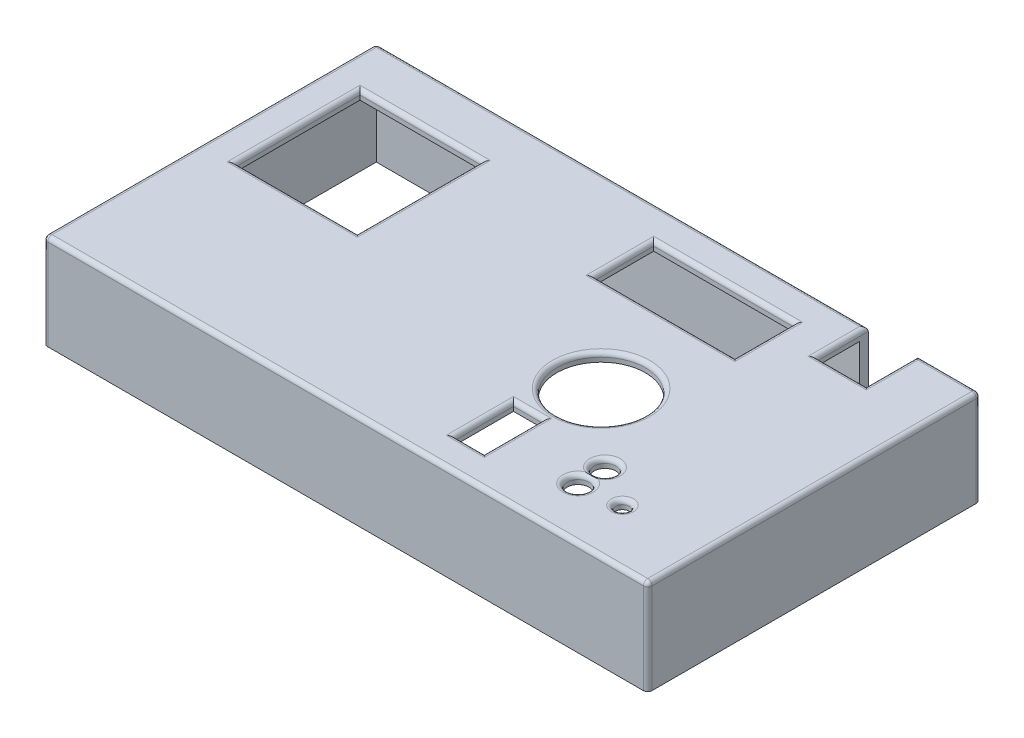
SolidWorks part; units mm, degrees
ref_plane "Front Plane" through (0, 0, 0) normal (0, 0, 1) x (1, 0, 0)
ref_plane "Top Plane" through (0, 0, 0) normal (0, 1, 0) x (1, 0, 0)
ref_plane "Right Plane" through (0, 0, 0) normal (1, 0, 0) x (0, 0, -1)
sketch "Sketch1" plane through (0, 0, 0) normal (0, 1, 0) x (1, 0, 0)
  line L0 (1.0429, 69.9365) -> (132.9972, 69.9365)
  line L1 (132.9972, 0.8484) -> (1.0429, 0.8484)
  line L2 (1.0429, 0.8484) -> (1.0429, 69.8095)
  line L3 (132.9972, 69.8095) -> (132.9972, 0.8484)
  line L4 (94.6421, 48.4741) -> (94.8961, 48.4741)
  line L5 (89.5621, 48.4741) -> (89.3081, 48.4741)
  line L6 (94.6421, 48.4741) -> (94.6421, 47.7121)
  line L7 (94.6421, 49.2361) -> (94.6421, 48.4741)
  line L8 (89.5621, 49.2361) -> (94.6421, 49.2361)
  line L9 (89.5621, 48.4741) -> (89.5621, 49.2361)
  line L10 (89.5621, 47.7121) -> (89.5621, 48.4741)
  line L11 (94.6421, 47.7121) -> (89.5621, 47.7121)
  line L12 (3.5161, 3.7303) -> (2.2461, 5.0003)
  line L13 (2.2461, 5.0003) -> (2.2461, 5.0145)
  line L14 (3.5161, 3.6429) -> (4.8731, 2.2859)
  line L15 (2.1446, 2.3221) -> (2.1953, 2.3221)
  line L16 (2.1953, 2.3221) -> (3.5161, 3.6429)
  line L17 (3.5161, 3.6429) -> (4.837, 4.9637)
  line L18 (4.837, 4.9637) -> (4.8878, 4.9637)
  line L19 (3.5161, 67.6973) -> (2.2461, 68.9673)
  line L20 (2.2461, 68.9673) -> (2.2461, 68.9814)
  line L21 (3.5161, 67.6099) -> (4.8731, 66.2529)
  line L22 (2.1446, 66.2891) -> (2.1953, 66.2891)
  line L23 (2.1953, 66.2891) -> (3.5161, 67.6099)
  line L24 (3.5161, 67.6099) -> (4.837, 68.9307)
  line L25 (4.837, 68.9307) -> (4.8878, 68.9307)
  line L26 (130.2022, 67.6975) -> (128.9322, 68.9675)
  line L27 (128.9322, 68.9675) -> (128.9322, 68.9817)
  line L28 (130.2022, 67.6101) -> (131.5591, 66.2532)
  line L29 (128.8306, 66.2893) -> (128.8814, 66.2893)
  line L30 (128.8814, 66.2893) -> (130.2022, 67.6101)
  line L31 (130.2022, 67.6101) -> (131.523, 68.9309)
  line L32 (131.523, 68.9309) -> (131.5738, 68.9309)
  line L33 (130.2022, 3.7303) -> (128.9322, 5.0003)
  line L34 (128.9322, 5.0003) -> (128.9322, 5.0145)
  line L35 (130.2022, 3.6429) -> (131.5591, 2.2859)
  line L36 (128.8306, 2.3221) -> (128.8814, 2.3221)
  line L37 (128.8814, 2.3221) -> (130.2022, 3.6429)
  line L38 (130.2022, 3.6429) -> (131.523, 4.9637)
  line L39 (131.523, 4.9637) -> (131.5738, 4.9637)
  line L40 (36.8771, 14.0372) -> (36.8771, 68.4373)
  line L41 (36.8771, 68.4373) -> (64.777, 68.4373)
  line L42 (64.777, 68.4373) -> (64.777, 14.0372)
  line L43 (64.777, 14.0372) -> (36.8771, 14.0372)
  line L44 (44.477, 62.8772) -> (44.477, 67.9572)
  line L45 (44.477, 67.9572) -> (45.747, 67.9572)
  line L46 (45.747, 67.9572) -> (45.747, 64.1472)
  line L47 (45.747, 64.1472) -> (47.017, 64.1472)
  line L48 (47.017, 64.1472) -> (47.017, 67.9572)
  line L49 (47.017, 67.9572) -> (48.287, 67.9572)
  line L50 (48.287, 67.9572) -> (48.287, 64.1472)
  line L51 (48.287, 64.1472) -> (49.557, 64.1472)
  line L52 (49.557, 64.1472) -> (49.557, 67.9572)
  line L53 (49.557, 67.9572) -> (50.827, 67.9572)
  line L54 (50.827, 67.9572) -> (50.827, 64.1472)
  line L55 (50.827, 64.1472) -> (52.097, 64.1472)
  line L56 (52.097, 64.1472) -> (52.097, 67.9572)
  line L57 (52.097, 67.9572) -> (53.367, 67.9572)
  line L58 (53.367, 67.9572) -> (53.367, 64.1472)
  line L59 (53.367, 64.1472) -> (54.637, 64.1472)
  line L60 (54.637, 64.1472) -> (54.637, 67.9572)
  line L61 (54.637, 67.9572) -> (55.907, 67.9572)
  line L62 (55.907, 67.9572) -> (55.907, 64.1472)
  line L63 (55.907, 64.1472) -> (58.447, 64.1472)
  line L64 (64.7971, 62.3171) -> (36.857, 62.3171)
  line L65 (36.857, 62.3171) -> (39.397, 62.3171)
  line L66 (39.397, 62.3171) -> (39.397, 13.911)
  line L67 (39.397, 13.911) -> (36.857, 13.911)
  line L68 (36.857, 13.911) -> (36.857, 62.3171)
  line L69 (62.257, 62.3171) -> (64.7971, 62.3171)
  line L70 (64.7971, 62.3171) -> (64.7971, 13.911)
  line L71 (64.7971, 13.911) -> (62.257, 13.911)
  line L72 (62.257, 13.911) -> (62.257, 62.3171)
  line L73 (110.4206, 7.58) -> (110.426, 10.1279)
  line L74 (110.2936, 13.93) -> (110.299, 16.4779)
  line L75 (73.1791, 8.342) -> (72.9251, 8.342)
  line L76 (78.2591, 8.342) -> (78.5131, 8.342)
  line L77 (73.1791, 8.342) -> (73.1791, 9.104)
  line L78 (73.1791, 7.58) -> (73.1791, 8.342)
  line L79 (78.2591, 7.58) -> (73.1791, 7.58)
  line L80 (78.2591, 8.342) -> (78.2591, 7.58)
  line L81 (78.2591, 9.104) -> (78.2591, 8.342)
  line L82 (73.1791, 9.104) -> (78.2591, 9.104)
  line L83 (118.7722, 25.233) -> (118.7722, 24.979)
  line L84 (118.7722, 30.3131) -> (118.7722, 30.5671)
  line L85 (118.7722, 25.233) -> (118.0102, 25.233)
  line L86 (119.5342, 25.233) -> (118.7722, 25.233)
  line L87 (119.5342, 30.3131) -> (119.5342, 25.233)
  line L88 (118.7722, 30.3131) -> (119.5342, 30.3131)
  line L89 (118.0102, 30.3131) -> (118.7722, 30.3131)
  line L90 (118.0102, 25.233) -> (118.0102, 30.3131)
  line L91 (75.7191, 48.7281) -> (75.9731, 48.7281)
  line L92 (70.6391, 48.7281) -> (70.3851, 48.7281)
  line L93 (75.7191, 48.7281) -> (75.7191, 47.9661)
  line L94 (75.7191, 49.4901) -> (75.7191, 48.7281)
  line L95 (70.6391, 49.4901) -> (75.7191, 49.4901)
  line L96 (70.6391, 48.7281) -> (70.6391, 49.4901)
  line L97 (70.6391, 47.9661) -> (70.6391, 48.7281)
  line L98 (75.7191, 47.9661) -> (70.6391, 47.9661)
  line L99 (127.9162, 32.5991) -> (127.9162, 32.3451)
  line L100 (127.9162, 37.6791) -> (127.9162, 37.9331)
  line L101 (127.9162, 32.5991) -> (127.1542, 32.5991)
  line L102 (128.6782, 32.5991) -> (127.9162, 32.5991)
  line L103 (128.6782, 37.6791) -> (128.6782, 32.5991)
  line L104 (127.9162, 37.6791) -> (128.6782, 37.6791)
  line L105 (127.1542, 37.6791) -> (127.9162, 37.6791)
  line L106 (127.1542, 32.5991) -> (127.1542, 37.6791)
  line L107 (102.2621, 8.723) -> (102.5161, 8.723)
  line L108 (97.1821, 8.723) -> (96.9281, 8.723)
  line L109 (102.2621, 8.723) -> (102.2621, 7.961)
  line L110 (102.2621, 9.485) -> (102.2621, 8.723)
  line L111 (97.1821, 9.485) -> (102.2621, 9.485)
  line L112 (97.1821, 8.723) -> (97.1821, 9.485)
  line L113 (97.1821, 7.961) -> (97.1821, 8.723)
  line L114 (102.2621, 7.961) -> (97.1821, 7.961)
  line L115 (102.2621, 14.946) -> (102.5161, 14.946)
  line L116 (97.1821, 14.946) -> (96.9281, 14.946)
  line L117 (102.2621, 14.946) -> (102.2621, 14.184)
  line L118 (102.2621, 15.708) -> (102.2621, 14.946)
  line L119 (97.1821, 15.708) -> (102.2621, 15.708)
  line L120 (97.1821, 14.946) -> (97.1821, 15.708)
  line L121 (97.1821, 14.184) -> (97.1821, 14.946)
  line L122 (102.2621, 14.184) -> (97.1821, 14.184)
  line L123 (88.4691, 65.5692) -> (101.0691, 65.5692)
  line L124 (88.4691, 52.9693) -> (101.0691, 52.9692)
  line L125 (88.4691, 65.5692) -> (88.4691, 63.2895)
  line L126 (88.4691, 60.329) -> (88.4691, 58.2095)
  line L127 (88.4691, 55.2489) -> (88.4691, 52.9693)
  line L128 (101.0691, 65.5692) -> (101.0691, 63.2895)
  line L129 (101.0691, 60.329) -> (101.0691, 58.2095)
  line L130 (101.0691, 55.2489) -> (101.0691, 52.9692)
  line L131 (69.5461, 65.6962) -> (82.1461, 65.6962)
  line L132 (69.5461, 53.0963) -> (82.1461, 53.0962)
  line L133 (69.5461, 65.6962) -> (69.5461, 63.4165)
  line L134 (69.5461, 60.456) -> (69.5461, 58.3365)
  line L135 (69.5461, 55.3759) -> (69.5461, 53.0963)
  line L136 (82.1461, 65.6962) -> (82.1461, 63.4165)
  line L137 (82.1461, 60.456) -> (82.1461, 58.3365)
  line L138 (82.1461, 55.3759) -> (82.1461, 53.0962)
  line L139 (91.2842, 17.3184) -> (85.4438, 17.3184)
  line L140 (85.4438, 17.3184) -> (85.4345, 17.309)
  line L141 (85.4345, 17.309) -> (85.4345, 4.709)
  line L142 (85.4345, 4.709) -> (91.2842, 4.709)
  line L143 (91.2842, 14.184) -> (89.6891, 14.184)
  line L144 (89.6891, 14.184) -> (89.6891, 12.914)
  line L145 (89.6891, 12.914) -> (91.2842, 12.914)
  line L146 (91.2842, 11.644) -> (89.6891, 11.644)
  line L147 (89.6891, 11.644) -> (89.6891, 10.374)
  line L148 (89.6891, 10.374) -> (91.2842, 10.374)
  line L149 (91.2842, 9.104) -> (89.6891, 9.104)
  line L150 (89.6891, 9.104) -> (89.6891, 7.834)
  line L151 (89.6891, 7.834) -> (91.2842, 7.834)
  line L152 (91.2842, 4.6996) -> (91.2842, 14.819)
  line L153 (91.2842, 14.819) -> (91.2842, 17.3184)
  line L154 (5.2238, 61.9788) -> (32.4221, 61.9788)
  line L155 (32.4221, 61.9788) -> (32.4221, 34.1784)
  line L156 (32.4221, 34.1784) -> (25.3228, 34.1784)
  line L157 (25.3228, 34.1784) -> (25.3228, 37.93)
  line L158 (25.3228, 37.93) -> (12.4729, 37.93)
  line L159 (12.4729, 37.93) -> (12.4729, 34.1784)
  line L160 (12.4729, 34.1784) -> (5.2238, 34.1784)
  line L161 (5.2238, 34.1784) -> (5.2238, 61.9788)
  line L162 (111.2791, 59.3188) -> (111.2791, 60.5611)
  line L163 (111.2791, 60.5611) -> (123.4712, 60.5611)
  line L164 (123.4712, 60.5611) -> (123.4712, 59.3188)
  line L165 (123.4712, 48.0035) -> (123.4712, 44.9611)
  line L166 (123.4712, 44.9611) -> (117.8621, 44.9611)
  line L167 (116.8882, 44.9611) -> (111.2791, 44.9611)
  line L168 (111.2791, 44.9611) -> (111.2791, 48.0035)
  line L169 (123.4712, 58.2035) -> (123.4712, 49.1189)
  line L170 (111.2791, 49.1189) -> (111.2791, 58.2035)
  line L171 (115.5972, 69.8811) -> (115.5972, 69.1831)
  line L172 (115.5972, 69.1831) -> (117.8539, 69.1831)
  line L173 (117.8539, 69.1831) -> (117.8539, 69.8811)
  line L174 (112.3512, 69.8811) -> (112.3512, 69.1831)
  line L175 (112.3512, 69.1831) -> (114.6079, 69.1831)
  line L176 (114.6079, 69.1831) -> (114.6079, 69.8811)
  line L177 (118.8992, 69.8811) -> (118.8992, 69.1831)
  line L178 (118.8992, 69.1831) -> (121.1559, 69.1831)
  line L179 (121.1559, 69.1831) -> (121.1559, 69.8811)
  line L180 (111.5331, 68.5401) -> (121.8202, 68.5401)
  line L181 (111.5331, 64.2221) -> (121.8202, 64.2221)
  line L182 (111.5331, 63.3331) -> (121.8202, 63.3331)
  line L183 (111.4901, 69.9082) -> (121.9902, 69.9082)
  line L184 (121.9902, 69.9082) -> (121.9902, 62.5081)
  line L185 (121.9902, 62.5081) -> (111.4901, 62.5081)
  line L186 (111.4901, 62.5081) -> (111.4901, 69.9082)
  line L187 (72.4171, 40.7271) -> (104.9291, 40.7271)
  line L188 (104.9291, 40.7271) -> (104.9291, 20.407)
  line L189 (104.9291, 20.407) -> (72.4171, 20.407)
  line L190 (72.4171, 20.407) -> (72.4171, 40.7271)
  line L191 (72.7981, 28.6621) -> (72.7981, 29.9321)
  line L192 (72.7981, 29.9321) -> (73.4331, 30.5671)
  line L193 (73.4331, 30.5671) -> (72.7981, 31.2021)
  line L194 (72.7981, 31.2021) -> (72.7981, 32.4721)
  line L195 (72.7981, 32.4721) -> (73.4331, 33.1071)
  line L196 (73.4331, 33.1071) -> (72.7981, 33.7421)
  line L197 (72.7981, 33.7421) -> (72.7981, 35.0121)
  line L198 (72.7981, 35.0121) -> (73.4331, 35.6471)
  line L199 (73.4331, 35.6471) -> (74.7031, 35.6471)
  line L200 (74.7031, 35.6471) -> (75.3381, 35.0121)
  line L201 (75.3381, 35.0121) -> (75.3381, 33.7421)
  line L202 (75.3381, 33.7421) -> (74.7031, 33.1071)
  line L203 (74.7031, 33.1071) -> (75.3381, 32.4721)
  line L204 (75.3381, 32.4721) -> (75.3381, 31.2021)
  line L205 (75.3381, 31.2021) -> (74.7031, 30.5671)
  line L206 (74.7031, 30.5671) -> (75.3381, 29.9321)
  line L207 (75.3381, 29.9321) -> (75.3381, 28.6621)
  line L208 (75.3381, 28.6621) -> (74.7031, 28.0271)
  line L209 (74.7031, 28.0271) -> (75.3381, 27.392)
  line L210 (75.3381, 27.392) -> (75.3381, 26.122)
  line L211 (75.3381, 26.122) -> (74.7031, 25.487)
  line L212 (74.7031, 25.487) -> (73.4331, 25.487)
  line L213 (73.4331, 25.487) -> (72.7981, 26.122)
  line L214 (72.7981, 26.122) -> (72.7981, 27.392)
  line L215 (72.7981, 27.392) -> (73.4331, 28.0271)
  line L216 (73.4331, 28.0271) -> (72.7981, 28.6621)
  line L217 (121.3792, 19.013) -> (126.5792, 19.013)
  line L218 (126.5792, 19.013) -> (126.5792, 16.213)
  line L219 (121.3792, 16.213) -> (126.5792, 16.213)
  line L220 (121.3792, 19.013) -> (121.3792, 16.213)
  line L221 (122.3384, 19.013) -> (122.3384, 16.213)
  line L222 (114.9022, 44.0321) -> (120.1022, 44.0321)
  line L223 (120.1022, 44.0321) -> (120.1022, 41.2321)
  line L224 (114.9022, 41.2321) -> (120.1022, 41.2321)
  line L225 (114.9022, 44.0321) -> (114.9022, 41.2321)
  line L226 (115.8614, 44.0321) -> (115.8614, 41.2321)
  line L227 (128.8801, 25.1329) -> (124.9203, 25.1329)
  line L228 (120.7521, 33.6419) -> (116.7923, 33.6419)
  line L229 (73.5575, 20.0235) -> (68.4775, 20.0235)
  line L230 (68.4775, 20.0235) -> (68.4775, 17.4835)
  line L231 (68.4775, 17.4835) -> (73.5575, 17.4835)
  line L232 (73.5575, 17.4835) -> (73.5575, 20.0235)
  line L233 (92.1024, 47.2041) -> (90.1378, 47.2041) construction
  line L234 (50.573, 20.661) -> (50.573, 51.2046) construction
  line L235 (53.394, 33.0669) -> (53.394, 42.9729) construction
  line L236 (106.4531, 8.596) -> (106.4531, 12.4536) construction
  line L237 (106.3261, 14.946) -> (106.3261, 18.8037) construction
  line L238 (117.5022, 27.7731) -> (117.5022, 29.7376) construction
  line L239 (73.1793, 47.4581) -> (71.2148, 47.4581) construction
  line L240 (126.6464, 35.1391) -> (126.6464, 37.1036) construction
  line L241 (100.8651, 7.072) -> (98.9006, 7.072) construction
  line L242 (99.7221, 13.676) -> (97.7576, 13.676) construction
  line L243 (84.8555, 10.8896) -> (84.8555, 12.8542) construction
  line L244 (110.8981, 52.625) -> (110.8981, 54.5895) construction
  arc A0 (5.4161, 3.6429) -> (5.4161, 3.6382) centre (3.5162, 3.6406) ccw
  arc A1 (5.4161, 67.6099) -> (5.4161, 67.6052) centre (3.5162, 67.6075) ccw
  arc A2 (132.1021, 67.6101) -> (132.1021, 67.6055) centre (130.2022, 67.6078) ccw
  arc A3 (132.1021, 3.6429) -> (132.1021, 3.6382) centre (130.2022, 3.6406) ccw
  arc A4 (125.5026, 9.612) -> (125.5014, 9.485) centre (118.3906, 9.6125) ccw
  arc A5 (119.9146, 9.104) -> (119.8274, 8.8936) centre (118.3905, 9.612) ccw
  arc A6 (110.4206, 10.1154) -> (110.4206, 7.58) centre (108.8737, 8.8477) ccw
  arc A7 (110.2936, 16.4655) -> (110.2936, 13.93) centre (108.7467, 15.1977) ccw
  arc A8 (128.8814, 25.1316) -> (124.919, 25.1316) centre (126.9002, 26.63) ccw
  arc A9 (120.7534, 33.6407) -> (116.791, 33.6407) centre (118.7722, 35.1391) ccw
  circle A10 centre (94.7671, 59.2706) radius 4.4981
  circle A11 centre (94.7691, 59.2691) radius 4.064
  circle A12 centre (75.844, 59.3976) radius 4.4981
  circle A13 centre (75.8461, 59.3961) radius 4.064
  circle A14 centre (92.4831, 30.5671) radius 9.779
  text T0 "R3" font "ARIAL" height 1.143
  text T1 "SCREW1" font "ARIAL" height 1.143
  text T2 "SCREW2" font "ARIAL" height 1.143
  text T3 "SCREW3" font "ARIAL" height 1.143
  text T4 "SCREW4" font "ARIAL" height 1.143
  text T5 "BUZ1" font "ARIAL" height 1.143
  text T6 "H1" font "ARIAL" height 1.143
  text T7 "ESP-WROOM-32 38 PIN" font "ARIAL" height 2.032
  text T8 "DEVKIT" font "ARIAL" height 2.032
  text T9 "LED2" font "ARIAL" height 1.143
  text T10 "LED3" font "ARIAL" height 1.143
  text T11 "R1" font "ARIAL" height 1.143
  text T12 "R2" font "ARIAL" height 1.143
  text T13 "R4" font "ARIAL" height 1.143
  text T14 "R5" font "ARIAL" height 1.143
  text T15 "R6" font "ARIAL" height 1.143
  text T16 "R7" font "ARIAL" height 1.143
  text T17 "SW2" font "ARIAL" height 1.143
  text T18 "SW3" font "ARIAL" height 1.143
  text T19 "U1" font "ARIAL" height 1.143
  text T20 "U3" font "ARIAL" height 1.143
  text T21 "U4" font "ARIAL" height 1.143
  text T22 "U5" font "ARIAL" height 1.143
  text T23 "&#96;SENSOR" font "ARIAL" height 1.27
  text T24 "U6" font "ARIAL" height 1.143
  text T25 "D3" font "ARIAL" height 1.143
  text T26 "D9" font "ARIAL" height 1.143
  text T27 "Q1" font "ARIAL" height 1.143
  text T28 "Q5" font "ARIAL" height 1.143
  text T29 "C6" font "ARIAL" height 1.143
sketch "Sketch2" plane through (0, 0, 0) normal (0, 1, 0) x (1, 0, 0)
  line L0 (-2.9571, 73.9365) -> (-2.9571, -3.1516)
  line L1 (1.0429, 69.9365) -> (132.9972, 69.9365) construction
  line L2 (1.0429, 69.9365) -> (1.0429, 0.8484) construction
  line L3 (1.0429, 0.8484) -> (132.9972, 0.8484) construction
  line L4 (132.9972, 69.9365) -> (132.9972, 0.8484) construction
  line L5 (-2.9571, -3.1516) -> (136.9972, -3.1516)
  line L6 (136.9972, 73.9365) -> (136.9972, -3.1516)
  line L7 (-2.9571, 73.9365) -> (136.9972, 73.9365)
  line L8 (-0.9571, 71.9365) -> (-0.9571, -1.1516)
  line L9 (-0.9571, -1.1516) -> (134.9972, -1.1516)
  line L10 (134.9972, 71.9365) -> (134.9972, -1.1516)
  line L11 (-0.9571, 71.9365) -> (134.9972, 71.9365)
  line L12 (110.9901, 62.0081) -> (110.9901, 73.9365)
  line L13 (111.4901, 62.5081) -> (121.9902, 62.5081) construction
  line L14 (111.4901, 62.5081) -> (111.4901, 75.6533) construction
  line L15 (111.4901, 75.6533) -> (121.9902, 75.6533) construction
  line L16 (121.9902, 62.5081) -> (121.9902, 75.6533) construction
  line L17 (110.9901, 76.1533) -> (122.4902, 76.1533)
  line L18 (122.4902, 62.0081) -> (122.4902, 76.1533)
  line L19 (110.9901, 62.0081) -> (122.4902, 62.0081)
  line L21 (110.9901, 62.0081) -> (110.9901, 76.1533) construction
  dimension "D1" = 4
  dimension "D2" = 2
  dimension "D3" = 0.5
extrude "Boss-Extrude3" add sketch "Sketch2" along normal blind 20 contours L18 L11 L10 L9 L8 L12 L7 L0 L5 L6 region at (54.0165, 0, -72.3387)
sketch "Sketch5" plane through (0, 20, 0) normal (0, 1, 0) x (1, 0, 0)
  line L0 (69.0461, 66.1962) -> (101.5691, 66.1962)
  line L1 (-2.9571, 73.9365) -> (136.9972, 73.9365)
  line L2 (-2.9571, 73.9365) -> (-2.9571, -3.1516)
  line L3 (-2.9571, -3.1516) -> (136.9972, -3.1516)
  line L4 (136.9972, 73.9365) -> (136.9972, -3.1516)
  line L5 (5.2238, 61.9788) -> (32.4221, 61.9788) construction
  line L6 (5.2238, 61.9788) -> (5.2238, 34.1784) construction
  line L7 (5.2238, 34.1784) -> (32.4221, 34.1784) construction
  line L8 (32.4221, 61.9788) -> (32.4221, 34.1784) construction
  line L9 (69.5461, 65.6962) -> (101.0691, 65.6962) construction
  line L10 (69.5461, 65.6962) -> (69.5461, 52.9692) construction
  line L11 (69.5461, 52.9692) -> (101.0691, 52.9692) construction
  line L12 (101.0691, 65.6962) -> (101.0691, 52.9692) construction
  line L13 (110.9901, 73.9365) -> (122.4902, 73.9365)
  line L14 (110.9901, 73.9365) -> (110.9901, 61.9788)
  line L15 (110.9901, 61.9788) -> (122.4902, 61.9788)
  line L16 (122.4902, 73.9365) -> (122.4902, 61.9788)
  line L17 (85.4438, 17.3184) -> (91.2842, 17.3184) construction
  line L18 (85.4438, 17.3184) -> (85.4438, 4.709) construction
  line L19 (85.4438, 4.709) -> (91.2842, 4.709) construction
  line L20 (91.2842, 17.3184) -> (91.2842, 4.709) construction
  line L21 (101.5691, 66.1962) -> (101.5691, 52.4692)
  line L22 (69.0461, 52.4692) -> (101.5691, 52.4692)
  line L23 (69.0461, 66.1962) -> (69.0461, 52.4692)
  line L24 (4.7238, 62.4788) -> (32.9221, 62.4788)
  line L25 (32.9221, 62.4788) -> (32.9221, 33.6784)
  line L26 (4.7238, 33.6784) -> (32.9221, 33.6784)
  line L27 (4.7238, 62.4788) -> (4.7238, 33.6784)
  line L28 (84.9438, 17.8184) -> (91.7842, 17.8184)
  line L29 (91.7842, 17.8184) -> (91.7842, 4.209)
  line L30 (84.9438, 4.209) -> (91.7842, 4.209)
  line L31 (84.9438, 17.8184) -> (84.9438, 4.209)
  circle A0 centre (92.4831, 30.5671) radius 9.779 construction
  circle A1 centre (118.3905, 9.612) radius 1.5842
  circle A2 centre (108.7467, 15.1977) radius 2.012 construction
  circle A3 centre (108.8737, 8.8477) radius 2.012 construction
  circle A4 centre (92.4831, 30.5671) radius 10.279
  circle A5 centre (108.7467, 15.1977) radius 2.512
  circle A6 centre (108.8737, 8.8477) radius 2.512
  line M34 (122.4902, 73.9365) -> (122.4902, 71.9365)
  line M35 (122.4902, 71.9365) -> (134.9972, 71.9365)
  line M36 (134.9972, 71.9365) -> (134.9972, -1.1516)
  line M37 (134.9972, -1.1516) -> (-0.9571, -1.1516)
  line M38 (-0.9571, -1.1516) -> (-0.9571, 71.9365)
  line M39 (-0.9571, 71.9365) -> (110.9901, 71.9365)
  line M40 (110.9901, 71.9365) -> (110.9901, 73.9365)
  line M41 (110.9901, 73.9365) -> (-2.9571, 73.9365)
  line M42 (-2.9571, 73.9365) -> (-2.9571, -3.1516)
  line M43 (-2.9571, -3.1516) -> (136.9972, -3.1516)
  line M44 (136.9972, -3.1516) -> (136.9972, 73.9365)
  line M45 (136.9972, 73.9365) -> (122.4902, 73.9365)
  dimension "D1" = 0.5
  dimension "D2" = 0.5
extrude "Boss-Extrude4" add sketch "Sketch5" along normal blind 2 contours L16 L15 L14 A6 A5 A4 A1 L31 L28 L29 L30 L27 L24 L25 L26 L23 L0 L21 L22 M35 M39 M38 M37 M36 | M45 M34 M35 M36 M37 M38 M39 M40 M41 M42 M43 M44 region at (54.0165, 20, -72.3387) region at (68.5999, 20, -32.9695)
fillet "Fillet3" radius 1 28 edges at (85.3076, 22, -52.4692) (101.5691, 22, -59.3327) (85.3076, 22, -66.1962) (69.0461, 22, -59.3327) (18.823, 22, -33.6784) (32.9221, 22, -48.0786) (18.823, 22, -62.4788) (4.7238, 22, -48.0786) (88.364, 22, -4.209) (91.7842, 22, -11.0137) (88.364, 22, -17.8184) (84.9438, 22, -11.0137) (118.3905, 22, -8.0278) (92.4831, 22, -20.288) (108.7467, 22, -12.6857) (108.8737, 22, -6.3357) (116.7402, 22, -61.9788) (122.4902, 22, -67.9576) (129.7437, 22, -73.9365) (136.9972, 22, -35.3925) (67.0201, 22, 3.1516) (-2.9571, 22, -35.3925) (54.0165, 22, -73.9365) (110.9901, 22, -67.9576) (-2.9571, 11, -73.9365) (-2.9571, 11, 3.1516) (136.9972, 11, 3.1516) (136.9972, 11, -73.9365)
